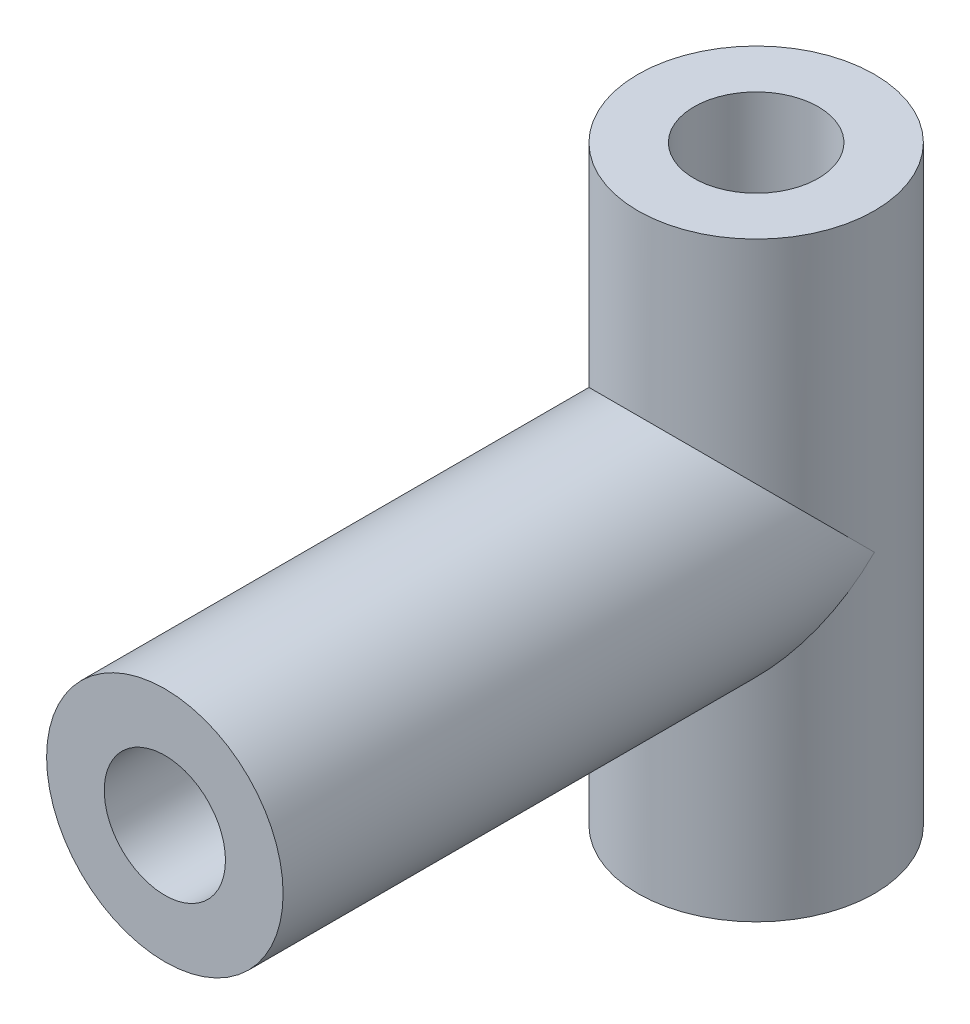
SolidWorks part; units mm, degrees
ref_plane "前基準面" through (0, 0, 0) normal (0, 0, 1) x (1, 0, 0)
ref_plane "上基準面" through (0, 0, 0) normal (0, 1, 0) x (1, 0, 0)
ref_plane "右基準面" through (0, 0, 0) normal (1, 0, 0) x (0, 0, -1)
sketch "草圖1" plane through (0, 0, 0) normal (0, 1, 0) x (1, 0, 0)
  circle A0 centre (0, 0) radius 4
  dimension "D1" = 8
extrude "填料-伸長1" add sketch "草圖1" along normal mid plane 20
sketch "草圖2" plane through (0, 0, 0) normal (0, 0, 1) x (1, 0, 0)
  circle A0 centre (0, 0) radius 4
extrude "填料-伸長2" add sketch "草圖2" along normal blind 20
sketch "草圖3" plane through (0, 0, 20) normal (0, 0, 1) x (1, 0, 0)
  circle A0 centre (0, 0) radius 2.05
  dimension "D1" = 4.1
extrude "除料-伸長1" cut sketch "草圖3" against normal blind 15
sketch "草圖4" plane through (0, -10, 0) normal (0, -1, 0) x (1, 0, 0)
  circle A0 centre (0, 0) radius 2.1
  dimension "D1" = 4.2
extrude "除料-伸長2" cut sketch "草圖4" against normal through all
